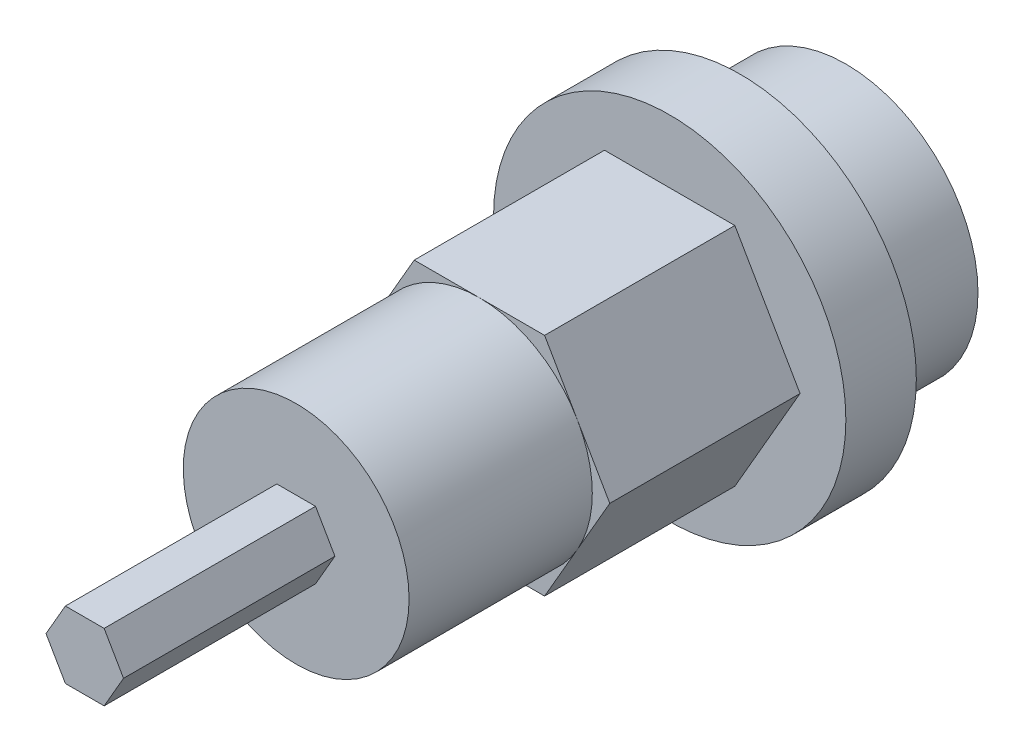
SolidWorks part; units mm, degrees
ref_plane "Front Plane" through (0, 0, 0) normal (0, 0, 1) x (1, 0, 0)
ref_plane "Top Plane" through (0, 0, 0) normal (0, 1, 0) x (1, 0, 0)
ref_plane "Right Plane" through (0, 0, 0) normal (1, 0, 0) x (0, 0, -1)
sketch "Sketch1" plane through (0, 0, 0) normal (0, 0, 1) x (1, 0, 0)
  circle A0 centre (0, 0) radius 3.75
  dimension "D1" = 7.5
extrude "Boss-Extrude1" add sketch "Sketch1" along normal blind 3
sketch "Sketch2" plane through (0, 0, 3) normal (0, 0, 1) x (1, 0, 0)
  circle A0 centre (0, 0) radius 5
  dimension "D1" = 10
extrude "Boss-Extrude2" add sketch "Sketch2" along normal blind 2
sketch "Sketch3" plane through (0, 0, 5) normal (0, 0, 1) x (1, 0, 0)
  line L7 (3.7, 0) -> (1.85, 3.2043)
  line L8 (1.85, 3.2043) -> (-1.85, 3.2043)
  line L9 (-1.85, 3.2043) -> (-3.7, 0)
  line L10 (-3.7, 0) -> (-1.85, -3.2043)
  line L11 (-1.85, -3.2043) -> (1.85, -3.2043)
  line L12 (1.85, -3.2043) -> (3.7, 0)
  circle A0 centre (0, 0) radius 3.7 construction
  circle A1 centre (0, 0) radius 3.2043 construction
  dimension "D1" = 7.4
extrude "Boss-Extrude3" add sketch "Sketch3" along normal blind 5.4
sketch "Sketch4" plane through (0, 0, 10.4) normal (0, 0, 1) x (1, 0, 0)
  line L2 (-1.85, 3.2043) -> (-3.7, 0) construction
  circle A0 centre (0, 0) radius 3.2043
extrude "Boss-Extrude4" add sketch "Sketch4" along normal blind 5.2
sketch "Sketch5" plane through (0, 0, 15.6) normal (0, 0, 1) x (1, 0, 0)
  line L1 (1.1, 0) -> (0.55, 0.9526)
  line L2 (0.55, 0.9526) -> (-0.55, 0.9526)
  line L3 (-0.55, 0.9526) -> (-1.1, 0)
  line L4 (-1.1, 0) -> (-0.55, -0.9526)
  line L5 (-0.55, -0.9526) -> (0.55, -0.9526)
  line L6 (0.55, -0.9526) -> (1.1, 0)
  circle A0 centre (0, 0) radius 0.9526 construction
  dimension "D1" = 1.1
extrude "Boss-Extrude5" add sketch "Sketch5" along normal blind 6
